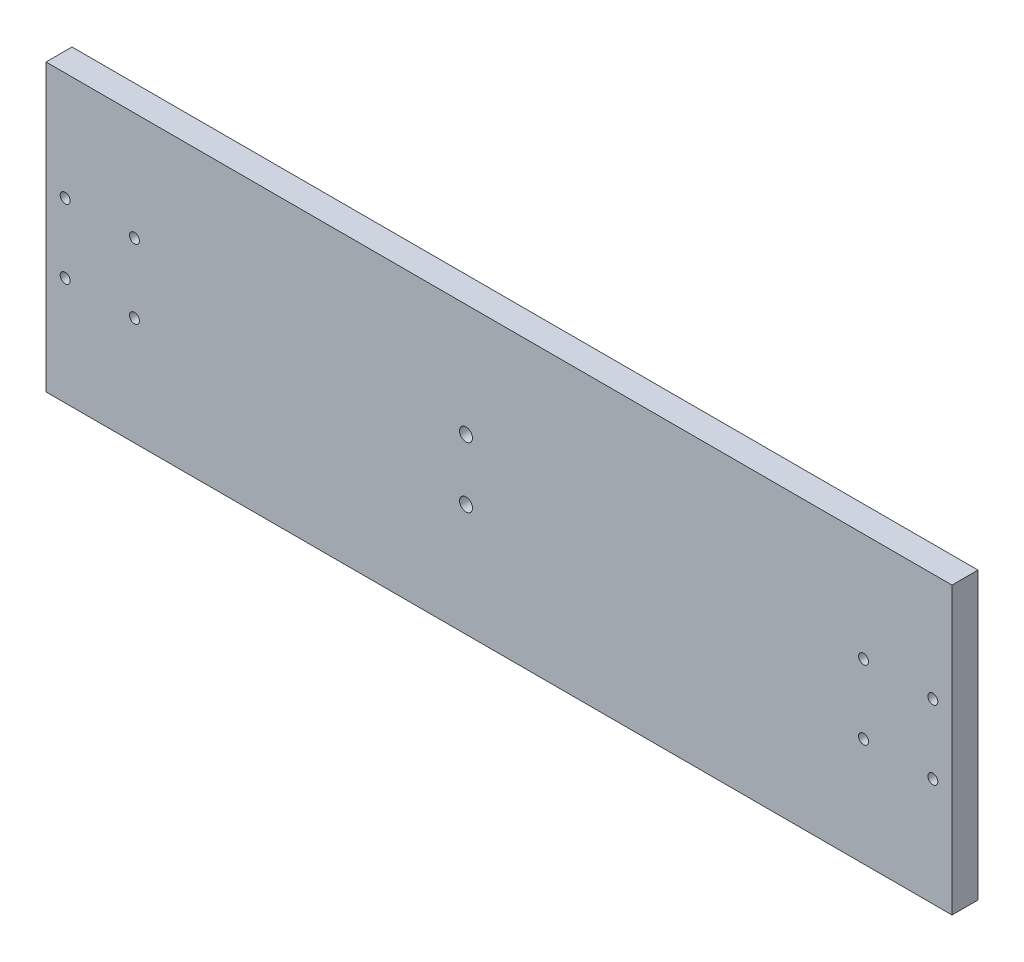
SolidWorks part; units mm, degrees
ref_plane "Plan de face" through (0, 0, 0) normal (0, 0, 1) x (1, 0, 0)
ref_plane "Plan de dessus" through (0, 0, 0) normal (0, 1, 0) x (1, 0, 0)
ref_plane "Plan de droite" through (0, 0, 0) normal (1, 0, 0) x (0, 0, -1)
sketch "Esquisse1" plane through (0, 0, 0) normal (0, 0, 1) x (1, 0, 0)
  line L1 (-104.63, 33) -> (104.63, 33)
  line L2 (-104.63, 33) -> (-104.63, -33)
  line L3 (-104.63, -33) -> (104.63, -33)
  line L4 (104.63, 33) -> (104.63, -33)
  dimension "D1" = 209.26
  dimension "D2" = 66
  dimension "D3" = 104.63
  dimension "D4" = 33
extrude "Boss.-Extru.1" add sketch "Esquisse1" along normal blind 6
sketch "Esquisse2" plane through (0, 0, 6) normal (0, 0, 1) x (1, 0, 0)
  line L0 (0, 49.0616) -> (0, -42.9956) construction
  line L1 (-104.63, 33) -> (-104.63, -33) construction
  line L2 (-104.63, -33) -> (104.63, -33) construction
  line L5 (-104.63, 33) -> (-104.63, -33) construction
  circle A0 centre (-100.2, 8) radius 1.15
  circle A1 centre (-84.2, 8) radius 1.15
  circle A2 centre (-84.2, -8) radius 1.15
  circle A3 centre (-100.2, -8) radius 1.15
  circle A4 centre (100.2, -8) radius 1.15
  circle A5 centre (84.2, -8) radius 1.15
  circle A6 centre (84.2, 8) radius 1.15
  circle A7 centre (100.2, 8) radius 1.15
  circle A8 centre (-7.625, 7) radius 1.5
  circle A9 centre (-7.625, -7) radius 1.5
  dimension "D1" = 2.3
  dimension "D2" = 2.3
  dimension "D3" = 2.3
  dimension "D4" = 2.3
  dimension "D12" = 3
  dimension "D14" = 3
  dimension "D13" = 26
  dimension "D15" = 7.625
  dimension "D5" = 4.43
  dimension "D6" = 25
  dimension "D7" = 25
  dimension "D8" = 16
  dimension "D9" = 16
  dimension "D10" = 16
  dimension "D11" = 16
  dimension "D16" = 14
  dimension "D17" = 7.625
  dimension "D18" = 4.43
extrude "Enlèv. mat.-Extru.1" cut sketch "Esquisse2" against normal blind 6
equation "\"D3@Esquisse1\"=\"D1@Esquisse1\"/2"
equation "\"D4@Esquisse1\"=\"D2@Esquisse1\"/2"
